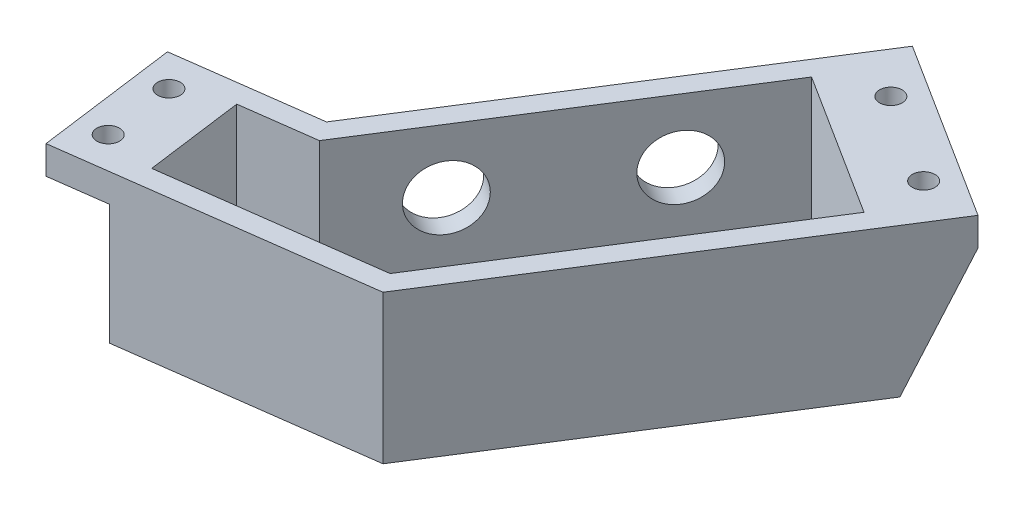
SolidWorks part; units mm, degrees
ref_plane "Спереди" through (0, 0, 0) normal (0, 0, 1) x (1, 0, 0)
ref_plane "Сверху" through (0, 0, 0) normal (0, 1, 0) x (1, 0, 0)
ref_plane "Справа" through (0, 0, 0) normal (1, 0, 0) x (0, 0, -1)
sketch "Sketch1" plane through (0, 0, 0) normal (0, 1, 0) x (1, 0, 0)
  line L0 (0, 0) -> (-19.8234, -2.6518)
  line L1 (-19.8234, -2.6518) -> (-17.1716, -22.4752)
  line L2 (-17.1716, -22.4752) -> (24.8344, -16.856)
  line L3 (24.8344, -16.856) -> (57.4678, 34.6043)
  line L4 (57.4678, 34.6043) -> (32.1325, 50.6705)
  line L5 (32.1325, 50.6705) -> (0, 0)
  line L6 (0, 0) -> (2.6518, -19.8234) construction
  dimension "D1" = 130
  dimension "D2" = 20
  dimension "D3" = 20
  dimension "D4" = 30
  dimension "D5" = 90
  dimension "D6" = 60
extrude "Boss-Extrude1" add sketch "Sketch1" along normal blind 21
sketch "Sketch2" plane through (0, 21, 0) normal (0, 1, 0) x (1, 0, 0)
  line L0 (32.1325, 50.6705) -> (27.8482, 43.9145)
  line L1 (32.1325, 50.6705) -> (0, 0) construction
  line L2 (27.8482, 43.9145) -> (53.1834, 27.8482)
  line L3 (24.8344, -16.856) -> (57.4678, 34.6043) construction
  line L4 (53.1834, 27.8482) -> (57.4678, 34.6043)
  line L5 (57.4678, 34.6043) -> (32.1325, 50.6705)
  line L6 (-19.8234, -2.6518) -> (-17.1716, -22.4752)
  line L7 (-17.1716, -22.4752) -> (-9.2422, -21.4145)
  line L8 (-17.1716, -22.4752) -> (24.8344, -16.856) construction
  line L9 (-9.2422, -21.4145) -> (-11.8941, -1.5911)
  line L10 (0, 0) -> (-19.8234, -2.6518) construction
  line L11 (-11.8941, -1.5911) -> (-19.8234, -2.6518)
  dimension "D1" = 8
extrude "Cut-Extrude1" cut sketch "Sketch2" along normal offset from surface (17 mm away) 4 from surface up to face at (12.9066, 21, -7.2153) starting at face at (12.9066, 0, -7.2153)
sketch "Sketch3" plane through (0, 21, 0) normal (0, 1, 0) x (1, 0, 0)
  line L0 (28.7751, 39.7743) -> (1.7843, -2.788)
  line L1 (1.7843, -2.788) -> (-8.5228, -4.1668)
  line L2 (-8.5228, -4.1668) -> (-6.6665, -18.0432)
  line L3 (-6.6665, -18.0432) -> (23.0501, -14.068)
  line L4 (23.0501, -14.068) -> (49.0433, 26.9213)
  line L5 (49.0433, 26.9213) -> (28.7751, 39.7743)
  line L6 (28.7751, 39.7743) -> (17.864, 23.073)
  line L7 (32.1325, 50.6705) -> (0, 0) construction
  line L9 (0, 0) -> (-19.8234, -2.6518) construction
  line L10 (-9.2422, -21.4145) -> (-11.8941, -1.5911) construction
  line L11 (-17.1716, -22.4752) -> (24.8344, -16.856) construction
  line L12 (24.8344, -16.856) -> (57.4678, 34.6043) construction
  line L13 (27.8482, 43.9145) -> (53.1834, 27.8482) construction
  dimension "D1" = 3
  dimension "D2" = 3
  dimension "D3" = 3
  dimension "D4" = 3
  dimension "D5" = 3
  dimension "D6" = 3
extrude "Cut-Extrude2" cut sketch "Sketch3" against normal offset from surface (18 mm away) 3 contours L4 L5 L0 L1 L2 L3 region at (21.3189, 21, -8.0208) up to face at (14.1216, 0, -5.3168)
sketch "Sketch4" plane through (2.5335, 0, 1.6066) normal (0.8445, 0, 0.5355) x (0.5355, 0, -0.8445)
  line L0 (11.6011, 3) -> (11.6011, 21) construction
  line L1 (49, 3) -> (-1.3989, 3) construction
  line L2 (-1.3989, 3) -> (-1.3989, 21) construction
  line L3 (49, 21) -> (-1.3989, 21) construction
  line L4 (1.1011, 4) -> (22.1011, 4) construction
  line L5 (1.1011, 4) -> (1.1011, 20) construction
  line L6 (1.1011, 20) -> (22.1011, 20) construction
  line L7 (22.1011, 4) -> (22.1011, 20) construction
  line L8 (1.1011, 4) -> (22.1011, 20) construction
  line L9 (1.1011, 20) -> (22.1011, 4) construction
  line L10 (11.6011, 12) -> (35.6011, 12) construction
  line L13 (25.1011, 4) -> (46.1011, 4) construction
  line L14 (25.1011, 4) -> (25.1011, 20) construction
  line L15 (25.1011, 20) -> (46.1011, 20) construction
  line L16 (46.1011, 4) -> (46.1011, 20) construction
  line L17 (25.1011, 4) -> (46.1011, 20) construction
  line L18 (25.1011, 20) -> (46.1011, 4) construction
  circle A0 centre (11.6011, 12) radius 4.5
  circle A1 centre (35.6011, 12) radius 4.5
  dimension "D1" = 9
  dimension "D2" = 16
  dimension "D5" = 24
  dimension "D3" = 21
  dimension "D4" = 13
extrude "Cut-Extrude3" cut sketch "Sketch4" against normal through all
sketch "Sketch5" plane through (0, 17, 0) normal (0, -1, 0) x (-1, 0, 0)
  line L0 (-29.9903, 47.2925) -> (-55.3256, 31.2262) construction
  line L1 (-32.1325, 50.6705) -> (-27.8482, 43.9145) construction
  line L2 (-53.1834, 27.8482) -> (-57.4678, 34.6043) construction
  line L3 (15.8587, -2.1215) -> (13.2069, -21.9449) construction
  line L4 (11.8941, -1.5911) -> (19.8234, -2.6518) construction
  line L5 (17.1716, -22.4752) -> (9.2422, -21.4145) construction
  line L8 (-32.1325, 50.6705) -> (-27.8482, 43.9145) construction
  circle A0 centre (-49.414, 34.975) radius 1.6
  circle A1 centre (-36.7464, 43.0082) radius 1.6
  circle A2 centre (13.8699, -16.989) radius 1.6
  circle A3 centre (15.1958, -7.0773) radius 1.6
  point P20 (14.5328, -12.0332)
  dimension "D1" = 3.2
  dimension "D2" = 10
  dimension "D3" = 5
  dimension "D4" = 15
  dimension "D5" = 8
extrude "Cut-Extrude4" cut sketch "Sketch5" against normal through all
sketch "Sketch6" plane through (0, 0, 0) normal (-0.8445, 0, -0.5355) x (-0.5355, 0, 0.8445)
  line L0 (-20, 0) -> (-20, 21) construction
  line L1 (-52, 0) -> (0, 0) construction
  line L2 (-60, 21) -> (0, 21) construction
  line L6 (0, 21) -> (0, 0) construction
  text T0 "<b>      OBS</b>" font "Arial" height 3
  dimension "D1" = 20
extrude "Cut-Extrude5" cut sketch "Sketch6" against normal blind 0.5
sketch "Sketch7" plane through (-8.9205, 0, 1.1933) normal (0.9912, 0, -0.1326) x (-0.1326, 0, -0.9912)
  line L0 (-10, 3) -> (-10, 21) construction
  line L1 (-3, 3) -> (-17, 3) construction
  line L2 (-3, 21) -> (-17, 21) construction
  circle A0 centre (-10, 10) radius 3
  dimension "D1" = 6
  dimension "D2" = 11
extrude "Cut-Extrude6" cut sketch "Sketch7" against normal through all
sketch "Sketch8" plane through (0, 0, 0) normal (-0.8445, 0, -0.5355) x (-0.5355, 0, 0.8445)
  line L0 (-52, 0) -> (-60, 17)
  line L1 (-60, 17) -> (-52, 17)
  line L2 (-52, 17) -> (-52, 0)
extrude "Boss-Extrude2" add sketch "Sketch8" against normal up to surface (30 mm away) up to face at (45.1619, 12.6667, -15.1988)
sketch "Sketch9" plane through (0, 21, 0) normal (0, 1, 0) x (1, 0, 0)
  circle A0 centre (36.7464, 43.0082) radius 1.6
  circle A1 centre (49.414, 34.975) radius 1.6
extrude "Cut-Extrude7" cut sketch "Sketch9" against normal through all
sketch "Sketch10" plane through (0, 21, 0) normal (0, 1, 0) x (1, 0, 0)
  circle A0 centre (36.7464, 43.0082) radius 3.5
  circle A1 centre (49.414, 34.975) radius 3.5
  dimension "D1" = 7
extrude "Cut-Extrude8" cut sketch "Sketch10" against normal through all from offset 4 offset against normal yes
sketch "Sketch11" plane through (0, 0, 0) normal (-0.1326, 0, -0.9912) x (-0.9912, 0, 0.1326)
  line L0 (7, 0) -> (7, 21) construction
  line L1 (0, 0) -> (12, 0) construction
  line L2 (0, 21) -> (20, 21) construction
  line L3 (12, 17) -> (12, 0) construction
  text T0 "<b>  1/ADF/2</b>" font "Arial" height 3
  dimension "D1" = 5
extrude "Cut-Extrude9" cut sketch "Sketch11" against normal blind 0.5
sketch "Sketch13" plane through (0, 0, 0) normal (-0.8445, 0, -0.5355) x (-0.5355, 0, 0.8445)
  line L0 (-44, 0) -> (-44, 21) construction
  line L1 (-52, 0) -> (0, 0) construction
  line L2 (-60, 21) -> (0, 21) construction
  text T0 "<b>      MAG</b>" font "Arial" height 3
  dimension "D1" = 8
extrude "Cut-Extrude11" cut sketch "Sketch13" against normal blind 0.5
